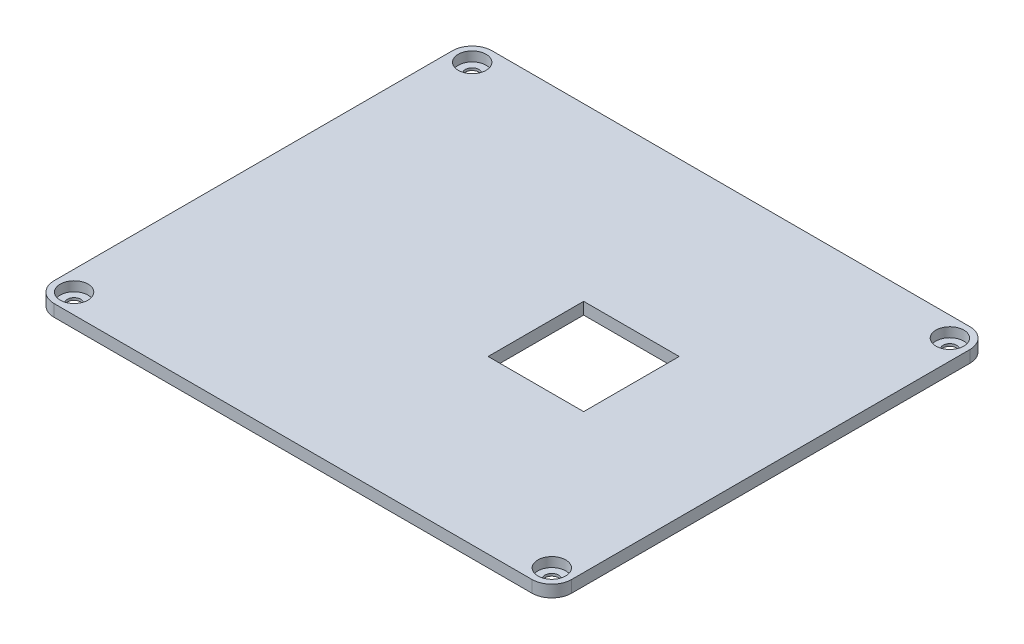
SolidWorks part; units mm, degrees
ref_plane "Front Plane" through (0, 0, 0) normal (0, 0, 1) x (1, 0, 0)
ref_plane "Top Plane" through (0, 0, 0) normal (0, 1, 0) x (1, 0, 0)
ref_plane "Right Plane" through (0, 0, 0) normal (1, 0, 0) x (0, 0, -1)
sketch "Sketch1" plane through (0, 0, 0) normal (0, 1, 0) x (1, 0, 0)
  line L1 (0, 0) -> (130, 0)
  line L2 (0, 0) -> (0, 110)
  line L3 (0, 110) -> (130, 110)
  line L4 (130, 0) -> (130, 110)
  dimension "D1" = 110
  dimension "D2" = 130
extrude "Boss-Extrude1" add sketch "Sketch1" along normal blind 3
hole_wizard "CBORE for M3 Pan Head Machine Screw1" positions "Sketch9" profile "Sketch8" counterbore size "M3" standard "ANSI Metric"
sketch "Sketch9" plane through (0, 3, 0) normal (0, 1, 0) x (1, 0, 0)
  line L0 (130, 110) -> (0, 110) construction
  line L1 (0, 110) -> (0, 0) construction
  line L2 (130, 0) -> (130, 110) construction
  line L3 (0, 0) -> (130, 0) construction
  point P0 (5, 105)
  point P2 (125, 105)
  point P4 (125, 5)
  point P6 (5, 5)
  dimension "D1" = 5
  dimension "D2" = 5
  dimension "D3" = 5
  dimension "D4" = 5
  dimension "D5" = 5
  dimension "D6" = 5
  dimension "D7" = 5
  dimension "D8" = 5
sketch "Sketch8" plane through (5, 3, -105) normal (1, 0, 0) x (0, 0, 1)
  line L0 (0, 0) -> (0, 8.0215)
  line L1 (0, 8.0215) -> (1.7, 7)
  line L2 (1.7, 7) -> (1.7, 2.4)
  line L3 (1.7, 2.4) -> (3.5, 2.4)
  line L4 (3.5, 2.4) -> (3.5, 0)
  line L5 (3.5, 0) -> (0, 0)
  line L10 (0, 8.0215) -> (-1.7, 7) construction
  line L11 (0, -6.35) -> (0, 107.95) construction
  dimension "Hole Dia." = 3.4
  dimension "Hole Depth" = 7
  dimension "C'Bore Dia." = 7
  dimension "C'Bore Depth" = 2.4
  dimension "Drill Angle" = 118
sketch "Sketch10" plane through (0, 3, 0) normal (0, 1, 0) x (1, 0, 0)
  line L2 (95, 67) -> (71, 67)
  line L3 (95, 67) -> (95, 43)
  line L4 (95, 43) -> (71, 43)
  line L5 (71, 67) -> (71, 43)
  line L6 (106.8035, 0) -> (106.8035, 110) construction
  line L7 (0, 0) -> (130, 0) construction
  line L8 (130, 110) -> (0, 110) construction
  line L9 (106.8035, 110) -> (106.8035, 55) construction
  line L10 (106.8035, 55) -> (126.9142, 55) construction
  line L11 (126.9142, 55) -> (-78.2244, 55) construction
  line L13 (130, 0) -> (130, 110) construction
  dimension "D1" = 24
  dimension "D2" = 24
  dimension "D3" = 43
  dimension "D4" = 35
extrude "Cut-Extrude1" cut sketch "Sketch10" against normal blind 5
fillet "Fillet1" radius 5 4 edges at (0, 1.5, -110) (0, 1.5, 0) (130, 1.5, -110) (130, 1.5, 0)
